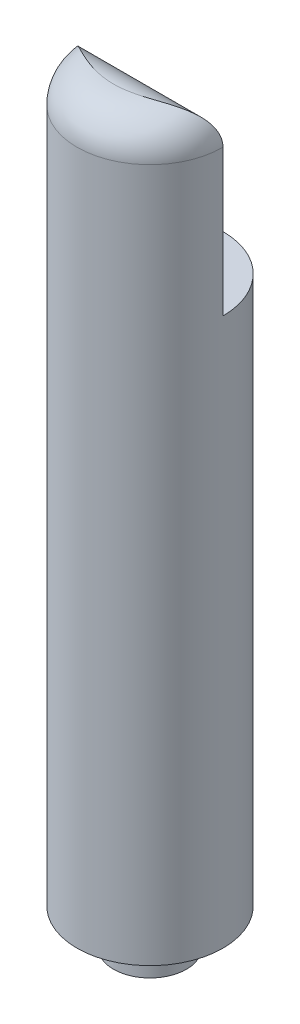
SolidWorks part; units mm, degrees
material "PE Low Density Film"
ref_plane "Front Plane" through (0, 0, 0) normal (0, 0, 1) x (1, 0, 0)
ref_plane "Top Plane" through (0, 0, 0) normal (0, 1, 0) x (1, 0, 0)
ref_plane "Right Plane" through (0, 0, 0) normal (1, 0, 0) x (0, 0, -1)
sketch "Sketch1" plane through (0, 0, 0) normal (0, 1, 0) x (1, 0, 0)
  circle A0 centre (0, 0) radius 10
  dimension "D1" = 20
extrude "Boss-Extrude1" add sketch "Sketch1" along normal blind 100
sketch "Sketch3" plane through (0, 0, 0) normal (0, 1, 0) x (1, 0, 0)
  circle A0 centre (0, 0) radius 5
sketch "Sketch4" plane through (0, 0, 0) normal (0, 0, 1) x (1, 0, 0)
  line L1 (10, 75) -> (-10, 75)
  line L2 (10, 75) -> (10, 100)
  line L3 (10, 100) -> (-10, 100)
  line L4 (-10, 75) -> (-10, 100)
  line L5 (10, 75) -> (-10, 100) construction
  line L6 (10, 100) -> (-10, 75) construction
  point P0 (0, 87.5)
  dimension "D1" = 25
extrude "Cut-Extrude2" cut sketch "Sketch4" against normal blind 10
sketch "Sketch7" plane through (0, 0, 0) normal (0, 0, 1) x (1, 0, 0)
  circle A0 centre (0, 92.0018) radius 5
fillet "Fillet3" radius 5 2 edges at (0, 100, 10) (0, 100, 0)
extrude "Boss-Extrude3" add sketch "Sketch3" against normal blind 5
extrude "Cut-Extrude3" cut sketch "Sketch7" along normal blind 5
